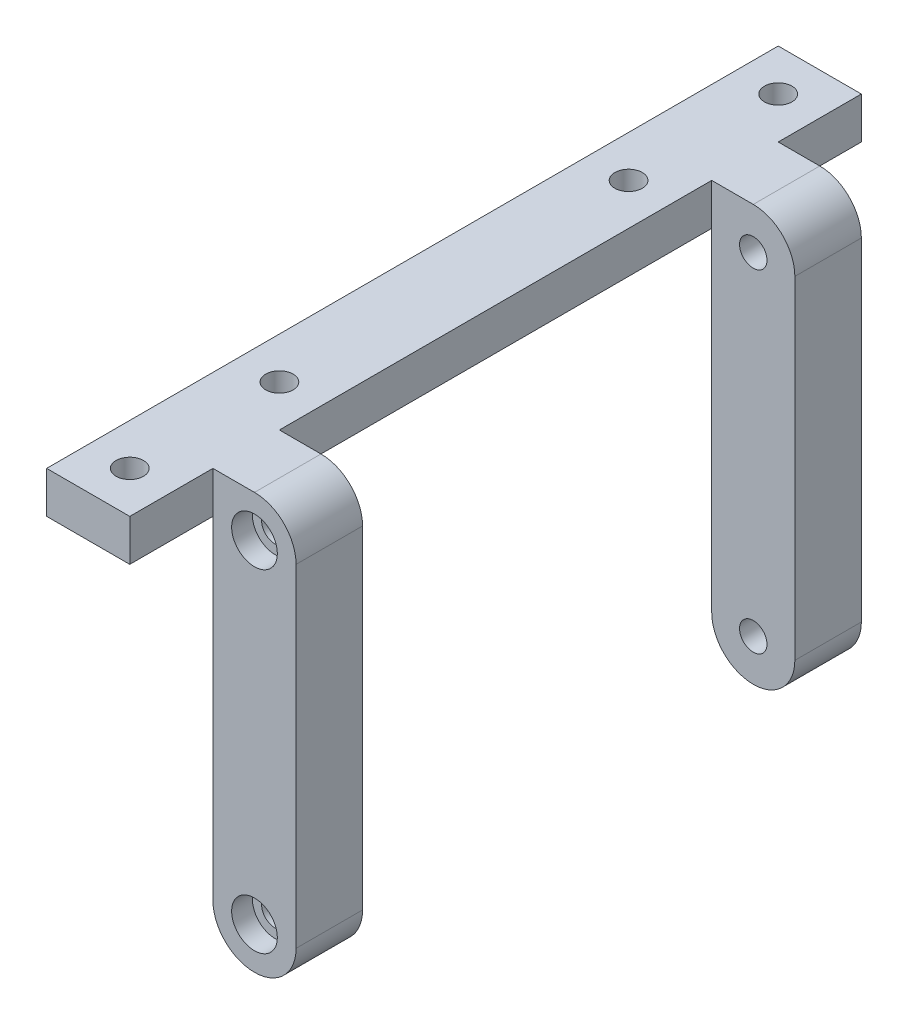
SolidWorks part; units mm, degrees
ref_plane "Přední rovina" through (0, 0, 0) normal (0, 0, 1) x (1, 0, 0)
ref_plane "Horní rovina" through (0, 0, 0) normal (0, 1, 0) x (1, 0, 0)
ref_plane "Pravá rovina" through (0, 0, 0) normal (1, 0, 0) x (0, 0, -1)
sketch "Skica1" plane through (0, 0, 0) normal (0, 0, 1) x (1, 0, 0)
  line L0 (0, 0) -> (10, 0)
  line L1 (10, 0) -> (10, 10)
  line L2 (10, 10) -> (8, 10)
  line L3 (8, 10) -> (8, 33)
  line L4 (8, 33) -> (10, 33)
  line L5 (10, 33) -> (10, 45)
  line L6 (10, 45) -> (0, 45)
  line L7 (0, 45) -> (0, 0)
  dimension "D1" = 45
  dimension "D2" = 10
  dimension "D3" = 8
  dimension "D4" = 10
  dimension "D5" = 12
  dimension "D6" = 10
extrude "Přidat vysunutím1" add sketch "Skica1" along normal blind 8
sketch "Skica2" plane through (0, 0, 8) normal (0, 0, 1) x (1, 0, 0)
  line L0 (0, 0) -> (10, 0) construction
  line L2 (10, 45) -> (0, 45) construction
  line L3 (0, 45) -> (0, 0) construction
  circle A0 centre (5, 45) radius 1.65
  circle A2 centre (5, 5) radius 1.65
  dimension "D1" = 3.3
  dimension "D3" = 3.3
  dimension "D4" = 5
  dimension "D6" = 0
  dimension "D7" = 5
  dimension "D9" = 5
extrude "Odebrat vysunutím1" cut sketch "Skica2" against normal through all
sketch "Skica3" plane through (0, 45, 0) normal (0, 1, 0) x (1, 0, 0)
  line L0 (0, 0) -> (0, 10)
  line L1 (0, 10) -> (-10, 10)
  line L2 (-10, 10) -> (-10, -18)
  line L3 (-10, -18) -> (0, -18)
  line L4 (0, -18) -> (0, -8)
  line L5 (0, -8) -> (10, -8)
  line L6 (10, -8) -> (10, 0)
  line L7 (10, 0) -> (0, 0)
  dimension "D1" = 10
  dimension "D2" = 10
  dimension "D3" = 10
extrude "Přidat vysunutím2" add sketch "Skica3" along normal blind 5
sketch "Skica4" plane through (0, 50, 0) normal (0, 1, 0) x (1, 0, 0)
  line L0 (-10, -18) -> (0, -18) construction
  line L1 (0, 10) -> (-10, 10) construction
  line L2 (0, 0) -> (0, 10) construction
  line L3 (0, -18) -> (0, -8) construction
  circle A0 centre (-5, 5) radius 1.65
  circle A1 centre (-5, -13) radius 1.65
  point P4 (-5, -18)
  point P11 (0, -13)
  dimension "D1" = 3.3
  dimension "D2" = 3.3
  dimension "D3" = 5
  dimension "D4" = 5
  dimension "D5" = 5
  dimension "D6" = 5
extrude "Odebrat vysunutím2" cut sketch "Skica4" against normal blind 5
sketch "Skica5" plane through (0, 0, 8) normal (0, 0, 1) x (1, 0, 0)
  line L0 (0, 50) -> (10, 50) construction
  line L1 (10, 33) -> (10, 50) construction
  circle A0 centre (5, 45) radius 1.65
  point P2 (5, 50)
  dimension "D1" = 3.3
  dimension "D2" = 5
  dimension "D3" = 5
extrude "Odebrat vysunutím3" cut sketch "Skica5" against normal through all
fillet "Zaoblit1" radius 5 3 edges at (0, 0, 4) (10, 0, 4) (10, 50, 4)
sketch "Skica6" plane through (0, 0, 8) normal (0, 0, 1) x (1, 0, 0)
  line L1 (10, 33) -> (8, 33)
  line L2 (10, 33) -> (10, 10)
  line L3 (10, 10) -> (8, 10)
  line L4 (8, 33) -> (8, 10)
extrude "Přidat vysunutím3" add sketch "Skica6" against normal blind 8
sketch "Skica7" plane through (0, 0, 8) normal (0, 0, 1) x (1, 0, 0)
  circle A0 centre (5, 5) radius 2.75
  circle A1 centre (5, 45) radius 2.75
  dimension "D1" = 5.5
  dimension "D2" = 5.5
extrude "Odebrat vysunutím4" cut sketch "Skica7" against normal blind 2.5
sketch "Skica8" plane through (0, 0, -10) normal (0, 0, -1) x (-1, 0, 0)
  line L1 (10, 50) -> (0, 50)
  line L2 (10, 50) -> (10, 45)
  line L3 (10, 45) -> (0, 45)
  line L4 (0, 50) -> (0, 45)
extrude "Přidat vysunutím4" add sketch "Skica8" along normal blind 60
sketch "Skica9" plane through (0, 0, 0) normal (1, 0, 0) x (0, 0, -1)
  line L0 (0, 50) -> (70, 50) construction
  line L1 (60, 50) -> (52, 50)
  line L2 (60, 50) -> (60, 45)
  line L3 (60, 45) -> (52, 45)
  line L4 (52, 50) -> (52, 45)
  line L5 (0, 45) -> (70, 45) construction
  line L6 (0, 50) -> (0, 45) construction
  line L10 (0, 45) -> (0, 5) construction
  line L11 (0, 5) -> (0, 45) construction
  point P18 (0, 25)
  point P21 (0, 25)
  dimension "D1" = 52
  dimension "D2" = 8
extrude "Přidat vysunutím5" add sketch "Skica9" along normal blind 10
sketch "Skica10" plane through (0, 45, 0) normal (0, -1, 0) x (1, 0, 0)
  line L1 (10, -60) -> (0, -60)
  line L2 (10, -60) -> (10, -52)
  line L3 (10, -52) -> (0, -52)
  line L4 (0, -60) -> (0, -52)
extrude "Přidat vysunutím6" add sketch "Skica10" along normal blind 45
fillet "Zaoblit2" radius 5 3 edges at (10, 50, -56) (10, 0, -56) (0, 0, -56)
sketch "Skica11" plane through (0, 0, -52) normal (0, 0, 1) x (1, 0, 0)
  line L0 (5, 50) -> (0, 50) construction
  line L1 (10, 45) -> (10, 5) construction
  circle A0 centre (5, 45) radius 1.65
  circle A1 centre (5, 5) radius 1.65
  dimension "D1" = 3.3
  dimension "D2" = 3.3
  dimension "D3" = 5
  dimension "D4" = 5
  dimension "D5" = 5
  dimension "D6" = 5
extrude "Odebrat vysunutím5" cut sketch "Skica11" against normal blind 45
sketch "Skica12" plane through (0, 0, -60) normal (0, 0, -1) x (-1, 0, 0)
  circle A0 centre (-5, 45) radius 2.75
  circle A1 centre (-5, 5) radius 2.75
  dimension "D1" = 5.5
  dimension "D2" = 5.5
extrude "Odebrat vysunutím6" cut sketch "Skica12" against normal blind 2.5
sketch "Skica13" plane through (0, 50, 0) normal (0, 1, 0) x (1, 0, 0)
  line L0 (-10, 70) -> (0, 70) construction
  line L1 (-10, 70) -> (-10, -18) construction
  line L2 (5, 60) -> (0, 60) construction
  circle A0 centre (-5, 65) radius 1.65
  circle A1 centre (-5, 47) radius 1.65
  dimension "D1" = 3.3
  dimension "D2" = 3.3
  dimension "D3" = 5
  dimension "D4" = 5
  dimension "D5" = 5
  dimension "D6" = 13
extrude "Odebrat vysunutím7" cut sketch "Skica13" against normal blind 12.5
